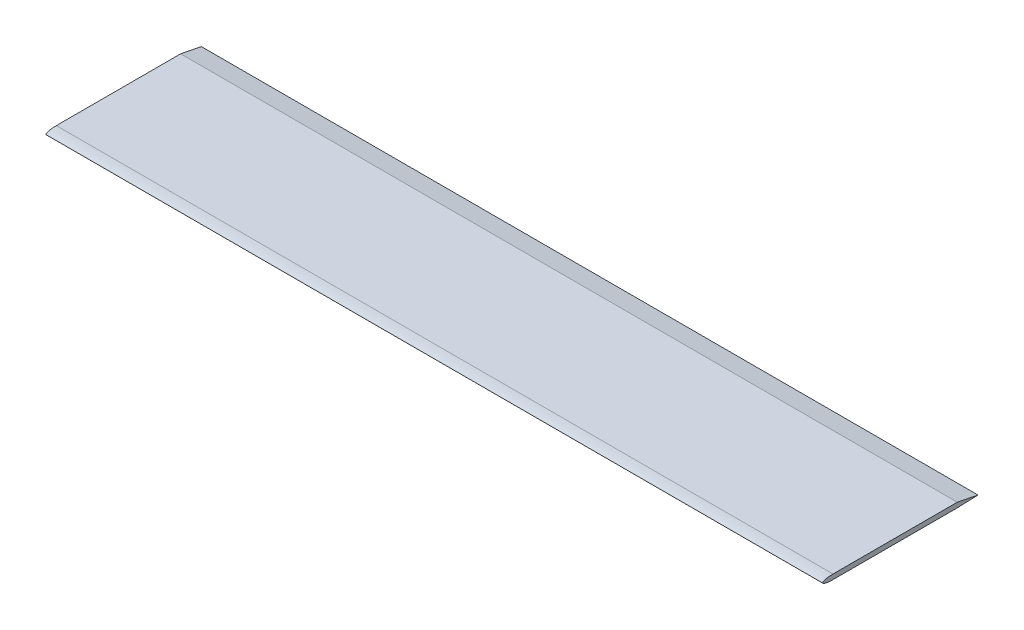
SolidWorks part; units mm, degrees
ref_plane "Front Plane" through (0, 0, 0) normal (0, 0, 1) x (1, 0, 0)
ref_plane "Top Plane" through (0, 0, 0) normal (0, 1, 0) x (1, 0, 0)
ref_plane "Right Plane" through (0, 0, 0) normal (1, 0, 0) x (0, 0, -1)
sketch "Sketch1" plane through (0, 0, 0) normal (1, 0, 0) x (0, 0, -1)
  line L3 (150.7285, 3) -> (176.1285, -2)
  line L4 (176.1285, -2) -> (150.7285, -3)
  line L5 (150.7285, 3) -> (-1.6715, 3)
  line L6 (150.7285, 3) -> (150.7285, -3)
  line L7 (150.7285, -3) -> (-1.6715, -3)
  line L8 (-1.6715, 3) -> (-1.6715, -3)
  ellipse E0 centre (-1.6715, 0) end of major axis (-14.3715, 0) minor radius 3
  dimension "D1" = 152.4
  dimension "D2" = 25.4
  dimension "D3" = 6
  dimension "D4" = 25.4
  dimension "D5" = 5
extrude "Boss-Extrude1" add sketch "Sketch1" along normal blind 952.5 contours E0 L7 L6 L5 | L8 E0 | L8 E0 | L3 L6 L4 region at (0, 0, -79.4875) region at (0, -0.6667, -159.1951) region at (0, 0, -3.7185) region at (0, 0, 7.0616)
